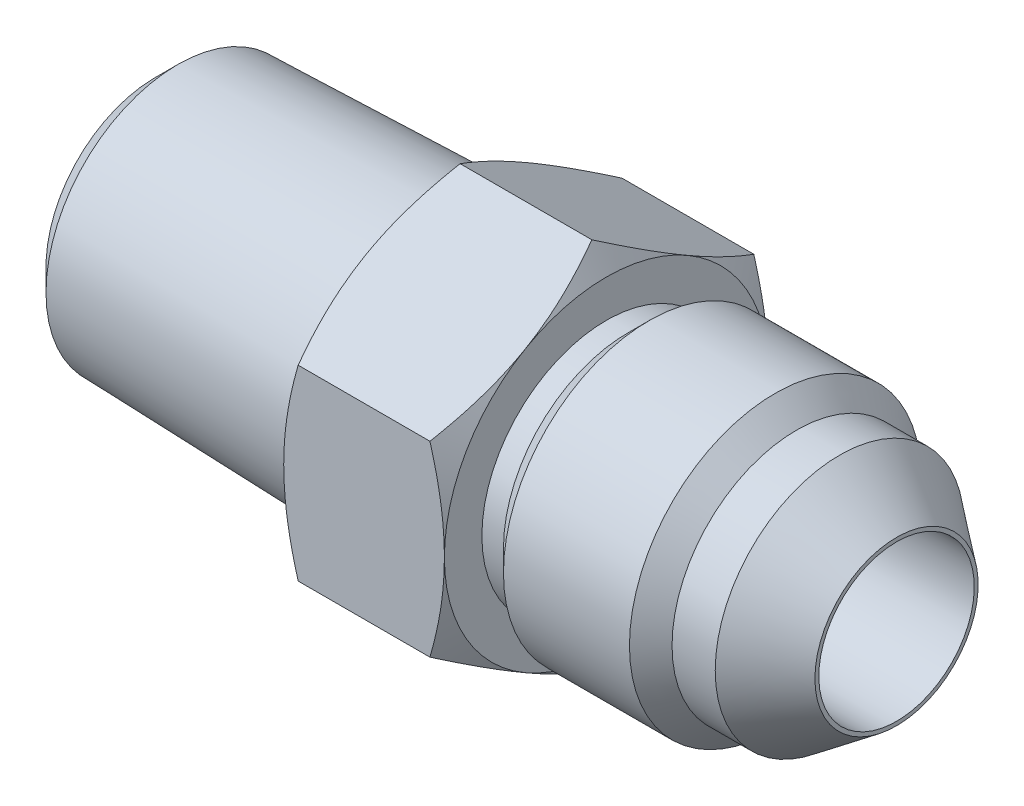
SolidWorks part; units mm, degrees
ref_plane "Front" through (0, 0, 0) normal (0, 0, 1) x (1, 0, 0)
ref_plane "Top" through (0, 0, 0) normal (0, 1, 0) x (1, 0, 0)
ref_plane "Right" through (0, 0, 0) normal (1, 0, 0) x (0, 0, -1)
sketch "Sketch6" plane through (0, 0, 0) normal (0, 0, 1) x (1, 0, 0)
  line L0 (-3.937, 6.858) -> (-3.937, -6.858) construction
  line L1 (18.161, 7.1438) -> (18.161, -7.1438) construction
  line L2 (-18.161, 0) -> (18.161, 0)
  line L4 (-18.161, 0) -> (-18.161, 7.1438)
  line L5 (-18.161, 7.1438) -> (18.161, 7.1438)
  line L6 (18.161, 0) -> (18.161, 7.1438)
  line L7 (-18.161, 3.556) -> (-18.161, -3.556) construction
  line L8 (-3.937, 8.6995) -> (-3.937, -8.6995) construction
  line L9 (3.937, 8.6995) -> (3.937, -8.6995) construction
  point P4 (3.937, 0)
  point P6 (-3.937, 0)
  dimension "Straight Dia" = 14.2875
  dimension "Length" = 36.322
  dimension "L1" = 14.224
  dimension "Pipe OD" = 13.716
  dimension "L2" = 14.224
  dimension "D1" = 7.112
  dimension "D2" = 17.399
revolve "Revolve3" add sketch "Sketch6" angle 360 about L2
sketch "Sketch14" plane through (18.161, 0, 0) normal (-1, 0, 0) x (0, 0, 1)
  circle A1 centre (0, 0) radius 7.1438
  circle A2 centre (0, 0) radius 7.1438
  dimension "D1" = 0
curve "Helix/Spiral1" pitch 1.4111 height 15.6351 turns 11.08 parameters "Pitch"=1.4111
sketch "Sketch15" plane through (0, 0, 0) normal (0, 0, 1) x (1, 0, 0)
  line L0 (18.161, 7.1438) -> (19.3957, 7.1438)
  line L1 (19.3957, 7.1438) -> (18.8666, 6.2272)
  line L2 (18.8666, 6.2272) -> (18.6902, 6.2272)
  line L3 (18.6902, 6.2272) -> (18.161, 7.1438)
  line L4 (18.7784, 6.2272) -> (18.7784, 7.1438) construction
  line L5 (18.4256, 6.6855) -> (19.1311, 6.6855) construction
  dimension "D1" = 60
  dimension "D2" = 0.1764
  dimension "D3" = 0.7056
sweep "Cut-Sweep1" [suppressed] cut profiles "Sketch15" path "Helix/Spiral1"
ref_plane "Plane1" through (-3.937, 0, 0) normal (1, 0, 0) x (0, 0, -1)
sketch "Sketch12" plane through (-3.937, 0, 0) normal (1, 0, 0) x (0, 0, -1)
  line L1 (0, 9.1654) -> (-7.9375, 4.5827)
  line L2 (-7.9375, 4.5827) -> (-7.9375, -4.5827)
  line L3 (-7.9375, -4.5827) -> (0, -9.1654)
  line L4 (0, -9.1654) -> (7.9375, -4.5827)
  line L5 (7.9375, -4.5827) -> (7.9375, 4.5827)
  line L6 (7.9375, 4.5827) -> (0, 9.1654)
  circle A0 centre (0, 0) radius 7.9375 construction
  dimension "Hex" = 15.875
extrude "Extrude1" add sketch "Sketch12" along normal up to vertex (7.874 mm away) up to point (3.937, 0, 0)
sketch "Sketch7" plane through (0, 0, 0) normal (0, 0, 1) x (1, 0, 0)
  line L0 (-18.161, 0) -> (-18.161, 3.81)
  line L2 (-18.161, 3.81) -> (18.161, 3.81)
  line L4 (18.161, 0) -> (18.161, 7.1438) construction
  line L11 (18.161, 3.81) -> (18.161, 0)
  line L12 (18.161, 0) -> (-18.161, 0)
  line L13 (-18.161, 3.81) -> (-18.161, -3.81) construction
  dimension "ID" = 7.62
sketch "Sketch10" plane through (0, 0, 0) normal (0, 0, 1) x (1, 0, 0)
  line L0 (-18.161, 7.1438) -> (18.161, 7.1438) construction
  line L1 (18.161, 7.1438) -> (19.3957, 7.1438) construction
  line L2 (-3.937, -6.858) -> (-18.161, -6.4233) construction
  line L3 (3.937, 9.1654) -> (3.937, 4.5827) construction
  line L5 (0, 0) -> (-18.161, 0) construction
  line L6 (6.0389, 7.1438) -> (3.937, 7.1438)
  line L9 (3.937, 6.1002) -> (3.937, 7.1438)
  line L21 (18.161, 7.1438) -> (12.2144, 7.1438)
  line L22 (12.2144, 7.1438) -> (13.2579, 6.1002)
  line L23 (13.2579, 6.1002) -> (15.3746, 6.1002)
  line L24 (15.3746, 6.1002) -> (18.161, 4.0005)
  line L25 (18.161, 4.0005) -> (18.161, 7.1438)
  line L26 (4.9953, 6.1002) -> (3.937, 6.1002)
  line L27 (6.0389, 7.1438) -> (4.9953, 6.1002)
  point P5 (10.4357, -7.1438)
  point P9 (-11.811, -6.6174)
  dimension "D1" = 8.001
  dimension "D2" = 37
  dimension "D3" = 2.1167
  dimension "D5" = 45
  dimension "D4" = 1.0583
  dimension "D6" = 2.8222
  dimension "D7" = 0.127
  dimension "D9" = 6.35
  dimension "D8" = 1.75
revolve "Cut-Revolve6" cut sketch "Sketch10" angle 360 about L2
revolve "Cut-Revolve5" cut sketch "Sketch7" angle 360 about L12
sketch "Sketch13" plane through (0, 0, 0) normal (0, 0, 1) x (1, 0, 0)
  line L0 (-3.937, 9.1654) -> (-3.937, 7.9375)
  line L1 (-3.937, 4.5827) -> (-3.937, 9.1654) construction
  line L2 (-3.937, 7.9375) -> (-3.2281, 9.1654)
  line L3 (-3.2281, 9.1654) -> (-3.937, 9.1654)
  line L4 (3.2281, 9.1654) -> (3.937, 7.9375)
  line L5 (3.937, 9.1654) -> (3.937, 4.5827) construction
  line L6 (3.937, 7.9375) -> (3.937, 9.1654)
  line L7 (3.937, 9.1654) -> (3.2281, 9.1654)
  dimension "D2" = 30
revolve "Cut-Revolve7" cut sketch "Sketch13" angle 360 about L2
sketch "Sketch17" plane through (-18.161, 0, 0) normal (-1, 0, 0) x (0, 0, 1)
  circle A0 centre (0, 0) radius 7.1438 construction
  circle A1 centre (0, 0) radius 7.1438
extrude "Cut-Extrude1" cut sketch "Sketch17" against normal up to vertex (14.224 mm away) up to point (-3.937, 0, 0)
ref_plane "Plane2" through (-3.937, 0, 0) normal (1, 0, 0) x (0, 0, -1)
sketch "Sketch19" plane through (-3.937, 0, 0) normal (1, 0, 0) x (0, 0, -1)
  circle A0 centre (0, 0) radius 6.858
extrude "Boss-Extrude1" add sketch "Sketch19" against normal up to vertex (14.224 mm away) draft 1.75 separate body up to point (-18.161, 0, 0)
sketch "Sketch20" plane through (-18.161, 0, 0) normal (1, 0, 0) x (0, 0, -1)
  circle A1 centre (0, 0) radius 6.4234
  circle A2 centre (0, 0) radius 6.4234 construction
sketch "Sketch21" plane through (0, 0, 0) normal (0, 0, 1) x (1, 0, 0)
  line L0 (-19.3641, 6.3033) -> (-18.2303, 6.3033) construction
  line L1 (-19.5028, 6.5435) -> (-18.7972, 5.3215) construction
  line L2 (-18.9173, 5.5295) -> (-18.6771, 5.5295)
  line L3 (-18.7972, 5.3215) -> (-18.0917, 6.5435) construction
  line L4 (-18.7972, 5.3215) -> (-18.6771, 5.5295) construction
  line L5 (-18.7972, 6.3033) -> (-18.7972, 6.5435) construction
  line L6 (-19.5028, 6.5435) -> (-18.0917, 6.5435) construction
  line L7 (-18.7972, 6.4234) -> (-18.161, 6.4234) construction
  line L8 (-18.0917, 6.5435) -> (-19.4334, 6.4234)
  line L9 (-19.4334, 6.4234) -> (-18.9173, 5.5295)
  line L10 (-18.6771, 5.5295) -> (-18.0917, 6.5435)
  line L11 (-18.7972, 5.3215) -> (-18.7972, 5.5295) construction
  dimension "D2" = 0.2402
  dimension "D1" = 1.4111
curve "Helix/Spiral2" parameters "Pitch"=1.4111
chamfer "Chamfer1" distance 1.0583 angle 45 1 edges at (-18.161, 0, -6.4234) first distance on face at (-18.161, 0, -6.4234)
sketch "Sketch22" plane through (-3.937, 0, 0) normal (1, 0, 0) x (0, 0, -1)
  circle A1 centre (0, 0) radius 6.858
  circle A2 centre (0, 0) radius 6.858
  dimension "D1" = 0
sweep "Cut-Sweep2" [suppressed] cut profiles "Sketch21" path "Helix/Spiral2"
extrude "Boss-Extrude3" add sketch "Sketch22" against normal up to vertex (14.224 mm away) draft 15 up to point (-18.161, 7.1438, 0)
combine bodies "Combine1" operation type add bodies to combine 173 169
sketch "Sketch23" plane through (-18.161, 0, 0) normal (-1, 0, 0) x (0, 0, 1)
  circle A2 centre (0, 0) radius 3.556
extrude "Cut-Extrude2" cut sketch "Sketch23" against normal up to vertex (14.224 mm away) up to point (-3.937, 0, 0)
equation "\"D3@Helix/Spiral1\" = \"L1@Sketch6\"+\"Pitch@Helix/Spiral1\""
equation "\"D2@Sketch15\" = \"Pitch@Helix/Spiral1\"*.125"
equation "\"D3@Sketch15\" = \"Pitch@Helix/Spiral1\"*.5"
equation "\"D3@Sketch10\" = \"Pitch@Helix/Spiral1\"*1.5"
equation "\"D1@Sketch10\" = \"ID@Sketch7\"*1.05"
equation "\"D1@Sketch21\" = \"Pitch@Helix/Spiral2\""
equation "\"D3@Helix/Spiral2\" = \"L2@Sketch6\"+\"Pitch@Helix/Spiral2\""
equation "\"D1@Chamfer1\" = \"Pitch@Helix/Spiral2\"*.75"
equation "\"D4@Sketch10\" = \"Pitch@Helix/Spiral1\"*.75"
equation "\"D6@Sketch10\" = \"Pitch@Helix/Spiral1\"*2"
equation "\"D9@Sketch10\" = \"Pitch@Helix/Spiral2\"*4.5"
equation "\"D2@Sketch6\" = \"Hex@Sketch12\"+.06"
